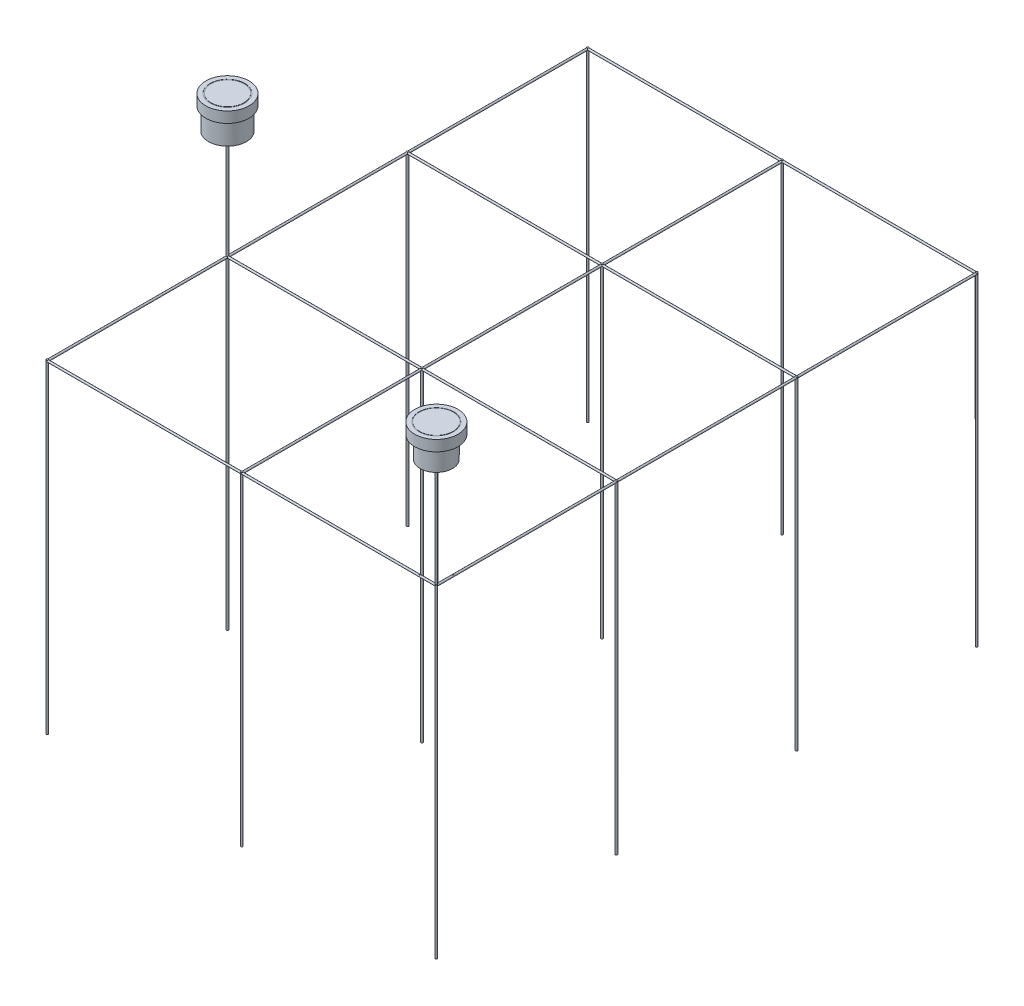
SolidWorks part; units mm, degrees
ref_plane "Alzado" through (0, 0, 0) normal (0, 0, 1) x (1, 0, 0)
ref_plane "Planta" through (0, 0, 0) normal (0, 1, 0) x (1, 0, 0)
ref_plane "Vista lateral" through (0, 0, 0) normal (1, 0, 0) x (0, 0, -1)
sketch "Croquis1" plane through (0, 0, 0) normal (0, 1, 0) x (1, 0, 0)
  circle A0 centre (0, 0) radius 9
  dimension "D1" = 18
extrude "Saliente-Extruir1" add sketch "Croquis1" against normal blind 3000
sketch "Croquis2" plane through (0, 0, 0) normal (0, 0, 1) x (1, 0, 0)
  line L0 (0, 0) -> (0, -9) construction
  circle A0 centre (0, -9) radius 9
  dimension "D1" = 9
extrude "Saliente-Extruir2" add sketch "Croquis2" against normal blind 5000
pattern_linear "MatrizL2" count 4 spacing 1666.6667 along (0, 0, -1) of "Saliente-Extruir1"
sketch "Croquis3" plane through (0, 0, 0) normal (1, 0, 0) x (0, 0, -1)
  line L0 (0, 0) -> (0, -9) construction
  line L1 (0, -9) -> (9, 0) construction
  line L2 (0, -9) -> (9, -18) construction
  circle A0 centre (0, -9) radius 9
extrude "Saliente-Extruir3" add sketch "Croquis3" along normal blind 3600
pattern_linear "MatrizL4" count 3 spacing 1800 along (1, 0, 0) of "Saliente-Extruir1"
pattern_linear "MatrizL5" count 3 spacing 1800 along (1, 0, 0) of "Saliente-Extruir2"
pattern_linear "MatrizL6" count 4 spacing 1666.6667 along (0, 0, -1) of "MatrizL4"
pattern_linear "MatrizL7" count 4 spacing 1666.6667 along (0, 0, -1) of "Saliente-Extruir3"
sketch "Croquis4" plane through (0, 0, 0) normal (0, 1, 0) x (1, 0, 0)
  circle A0 centre (0, 1666.6667) radius 9
extrude "Saliente-Extruir4" add sketch "Croquis4" along normal blind 1300
sketch "Croquis5" plane through (0, 1300, 0) normal (0, 1, 0) x (1, 0, 0)
  circle A0 centre (0, 1666.6667) radius 200
  dimension "D1" = 400
extrude "Saliente-Extruir5" add sketch "Croquis5" against normal blind 100
sketch "Croquis6" plane through (0, 1200, 0) normal (0, -1, 0) x (1, 0, 0)
  circle A0 centre (0, -1666.6667) radius 175
  dimension "D1" = 350
extrude "Saliente-Extruir6" add sketch "Croquis6" along normal blind 200
ref_plane "Plano1" through (0, 1, 0) normal (0, 1, 0) x (1, 0, 0)
sketch "Croquis9" plane through (0, 1, 0) normal (0, 1, 0) x (1, 0, 0)
  circle A0 centre (3600, 0) radius 9.1043
extrude "Saliente-Extruir10" add sketch "Croquis9" along normal blind 1300 separate body
sketch "Croquis10" plane through (0, 1301, 0) normal (0, 1, 0) x (1, 0, 0)
  circle A0 centre (3600, 0) radius 200
  dimension "D1" = 400
extrude "Saliente-Extruir11" add sketch "Croquis10" against normal blind 100
sketch "Croquis11" plane through (0, 1300, 0) normal (0, 1, 0) x (1, 0, 0)
  circle A0 centre (0, 1666.6667) radius 160
  circle A1 centre (0, 1666.6667) radius 151.5948
  dimension "D1" = 320
extrude "Cortar-Extruir1" cut sketch "Croquis11" against normal blind 2
sketch "Croquis12" plane through (0, 1, 0) normal (0, 1, 0) x (1, 0, 0)
  circle A0 centre (3601.1557, 0) radius 160
  circle A1 centre (3601.1557, 0) radius 148.3302
  dimension "D1" = 320
extrude "Cortar-Extruir2" cut sketch "Croquis12" against normal blind 2
sketch "Croquis13" plane through (0, 1301, 0) normal (0, 1, 0) x (1, 0, 0)
  circle A0 centre (3600, 0) radius 160
  circle A1 centre (3600, 0) radius 155
  dimension "D1" = 320
  dimension "D2" = 5
extrude "Cortar-Extruir3" cut sketch "Croquis13" against normal blind 2
sketch "Croquis14" plane through (0, 0, 0) normal (0, 1, 0) x (1, 0, 0)
  line L0 (0, 5009) -> (0, 4991) construction
  arc A0 (0, 4991) -> (6.364, 4993.636) centre (0, 5000) ccw construction
  arc A1 (0, 4991) -> (9, 5000) centre (0, 5000) ccw construction
ref_plane "Plano2" through (0, 0, 0) normal (-1, 0, 0) x (0, 0, 1)
sketch "Croquis15" plane through (0, 1201, 0) normal (0, -1, 0) x (1, 0, 0)
  circle A0 centre (3600, 0) radius 150
  dimension "D1" = 300
extrude "Saliente-Extruir12" add sketch "Croquis15" along normal blind 200
sketch "Croquis16" plane through (0, 0, 0) normal (0, 1, 0) x (1, 0, 0)
  line L0 (1809, 2500) -> (1791, 2500) construction
  line L1 (1809, 1675.6667) -> (1809, 3324.3333) construction
  line L2 (1791, 3324.3333) -> (1791, 1675.6667) construction
  line L3 (1791, 2500) -> (1800, 2500) construction
  line L4 (1800, 2500) -> (1800, -18.722) construction
  line L5 (1800, 2500) -> (-376.0024, 2500) construction
ref_plane "Plano3" through (1800, 0, 0) normal (-1, 0, 0) x (0, 0, 1)
ref_plane "Plano4" through (0, 0, -2500) normal (0, 0, -1) x (-1, 0, 0)
